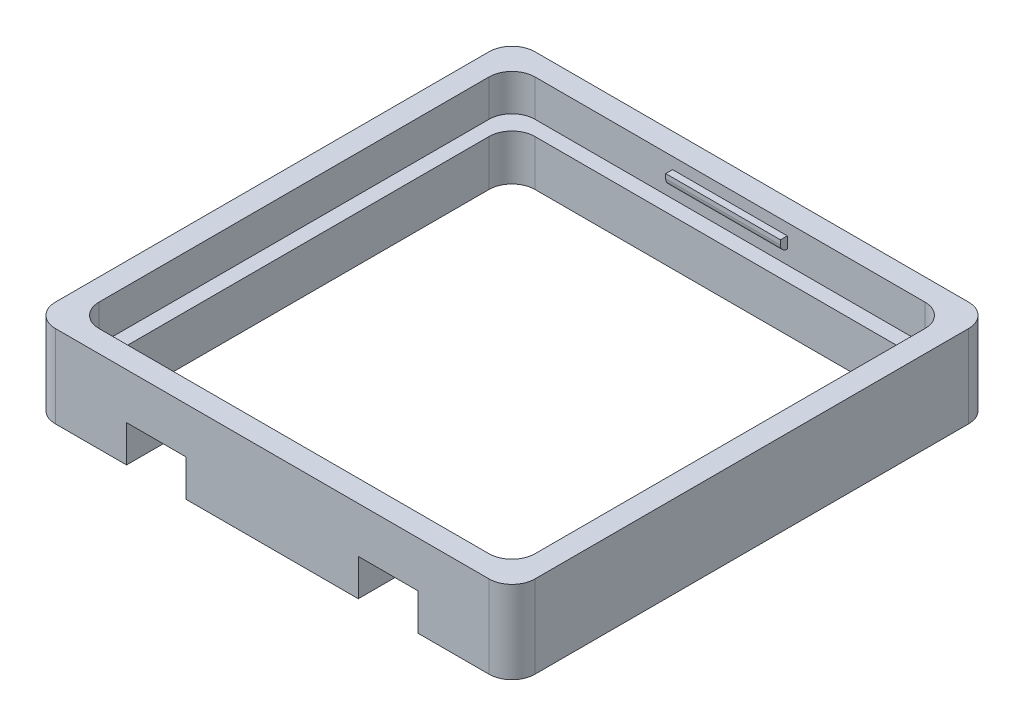
SolidWorks part; units mm, degrees
ref_plane "Front Plane" through (0, 0, 0) normal (0, 0, 1) x (1, 0, 0)
ref_plane "Top Plane" through (0, 0, 0) normal (0, 1, 0) x (1, 0, 0)
ref_plane "Right Plane" through (0, 0, 0) normal (1, 0, 0) x (0, 0, -1)
sketch "Sketch1" plane through (0, 0, 0) normal (0, 1, 0) x (1, 0, 0)
  line L1 (-24.003, -26.543) -> (24.003, -26.543)
  line L2 (-26.543, -24.003) -> (-26.543, 24.003)
  line L3 (-24.003, 26.543) -> (24.003, 26.543)
  line L4 (26.543, -24.003) -> (26.543, 24.003)
  line L5 (-26.543, -26.543) -> (26.543, 26.543) construction
  line L6 (-26.543, 26.543) -> (26.543, -26.543) construction
  arc A0 (-24.003, -26.543) -> (-26.543, -24.003) centre (-24.003, -24.003) cw
  arc A1 (24.003, -26.543) -> (26.543, -24.003) centre (24.003, -24.003) ccw
  arc A2 (24.003, 26.543) -> (26.543, 24.003) centre (24.003, 24.003) cw
  arc A3 (-26.543, 24.003) -> (-24.003, 26.543) centre (-24.003, 24.003) cw
  point P0 (0, 0)
  dimension "D3" = 2.54
  dimension "D1" = 53.086
  dimension "D2" = 53.086
extrude "Boss-Extrude2" add sketch "Sketch1" along normal blind 9.144
sketch "Sketch2" plane through (0, 0, 26.543) normal (0, 0, 1) x (1, 0, 0)
  line L0 (9.525, 4.064) -> (16.129, 4.064)
  line L1 (-16.129, -4.064) -> (-9.525, -4.064)
  line L2 (-16.129, -4.064) -> (-16.129, 4.064)
  line L3 (-16.129, 4.064) -> (-9.525, 4.064)
  line L4 (16.129, -4.064) -> (16.129, 4.064)
  line L5 (-16.129, -4.064) -> (16.129, 4.064) construction
  line L6 (-16.129, 4.064) -> (16.129, -4.064) construction
  line L8 (-9.525, -4.064) -> (-9.525, 4.064)
  line L10 (9.525, -4.064) -> (9.525, 4.064)
  line L11 (-9.525, -4.064) -> (9.525, 4.064) construction
  line L12 (-9.525, 4.064) -> (9.525, -4.064) construction
  line L13 (9.525, -4.064) -> (16.129, -4.064)
  point P0 (0, 0)
  point P6 (0, 0)
  dimension "D1" = 8.128
  dimension "D2" = 32.258
  dimension "D3" = 19.05
extrude "Cut-Extrude1" cut sketch "Sketch2" against normal blind 49.022
sketch "Sketch5" plane through (0, 9.144, 0) normal (0, 1, 0) x (1, 0, 0)
  line L1 (-19.939, -22.479) -> (19.939, -22.479)
  line L2 (-22.479, -19.939) -> (-22.479, 19.939)
  line L3 (-19.939, 22.479) -> (19.939, 22.479)
  line L4 (22.479, -19.939) -> (22.479, 19.939)
  line L5 (-22.479, -22.479) -> (22.479, 22.479) construction
  line L6 (-22.479, 22.479) -> (22.479, -22.479) construction
  arc A0 (-22.479, 19.939) -> (-19.939, 22.479) centre (-19.939, 19.939) cw
  arc A1 (19.939, 22.479) -> (22.479, 19.939) centre (19.939, 19.939) cw
  arc A2 (19.939, -22.479) -> (22.479, -19.939) centre (19.939, -19.939) ccw
  arc A3 (-19.939, -22.479) -> (-22.479, -19.939) centre (-19.939, -19.939) cw
  point P0 (0, 0)
  dimension "D3" = 2.54
  dimension "D1" = 44.958
  dimension "D2" = 44.958
extrude "Cut-Extrude3" cut sketch "Sketch5" against normal through all
sketch "Sketch6" plane through (0, 9.144, 0) normal (0, 1, 0) x (1, 0, 0)
  line L1 (-21.59, -24.13) -> (21.59, -24.13)
  line L2 (-24.13, -21.59) -> (-24.13, 21.59)
  line L3 (-21.59, 24.13) -> (21.59, 24.13)
  line L4 (24.13, -21.59) -> (24.13, 21.59)
  line L5 (-24.13, -24.13) -> (24.13, 24.13) construction
  line L6 (-24.13, 24.13) -> (24.13, -24.13) construction
  arc A0 (-21.59, -24.13) -> (-24.13, -21.59) centre (-21.59, -21.59) cw
  arc A1 (21.59, -24.13) -> (24.13, -21.59) centre (21.59, -21.59) ccw
  arc A2 (21.59, 24.13) -> (24.13, 21.59) centre (21.59, 21.59) cw
  arc A3 (-24.13, 21.59) -> (-21.59, 24.13) centre (-21.59, 21.59) cw
  point P1 (0, 0)
  dimension "D3" = 2.54
  dimension "D1" = 48.26
  dimension "D2" = 48.26
extrude "Cut-Extrude4" cut sketch "Sketch6" against normal blind 4.064
sketch "Sketch7" plane through (0, 0, -24.13) normal (0, 0, 1) x (1, 0, 0)
  line L0 (21.59, 9.144) -> (-21.59, 9.144) construction
  line L1 (-6.35, 6.604) -> (6.35, 6.604)
  line L2 (-6.35, 6.604) -> (-6.35, 7.874)
  line L3 (-6.35, 7.874) -> (6.35, 7.874)
  line L4 (6.35, 6.604) -> (6.35, 7.874)
  line L5 (-6.35, 6.604) -> (6.35, 7.874) construction
  line L6 (-6.35, 7.874) -> (6.35, 6.604) construction
  line L7 (19.939, 5.08) -> (-19.939, 5.08) construction
  point P0 (0, 7.239)
  point P9 (0, 5.08)
  dimension "D1" = 1.27
  dimension "D2" = 2.54
  dimension "D3" = 12.7
  dimension "D4" = 0
extrude "Boss-Extrude3" add sketch "Sketch7" along normal blind 0.762
fillet "Fillet1" radius 0.762 1 edges at (0, 6.604, -23.368)
sketch "Sketch8" plane through (0, 0, 24.13) normal (0, 0, -1) x (-1, 0, 0)
  line L0 (19.939, 5.08) -> (-19.939, 5.08) construction
  line L1 (-6.35, 6.604) -> (6.35, 6.604)
  line L2 (-6.35, 6.604) -> (-6.35, 7.874)
  line L3 (-6.35, 7.874) -> (6.35, 7.874)
  line L4 (6.35, 6.604) -> (6.35, 7.874)
  line L5 (-6.35, 6.604) -> (6.35, 7.874) construction
  line L6 (-6.35, 7.874) -> (6.35, 6.604) construction
  line L7 (21.59, 9.144) -> (-21.59, 9.144) construction
  point P0 (0, 7.239)
  point P7 (0, 5.08)
  dimension "D1" = 1.27
  dimension "D2" = 12.7
  dimension "D3" = 0
  dimension "D4" = 2.54
